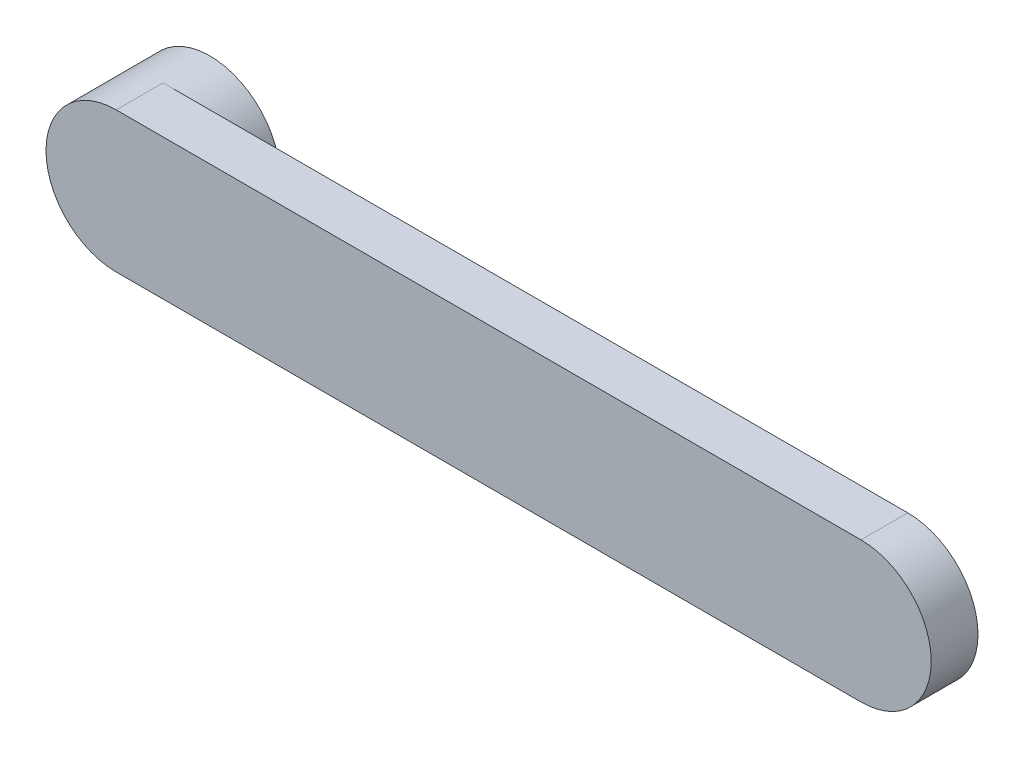
SolidWorks part; units mm, degrees
ref_plane "前视基准面" through (0, 0, 0) normal (0, 0, 1) x (1, 0, 0)
ref_plane "上视基准面" through (0, 0, 0) normal (0, 1, 0) x (1, 0, 0)
ref_plane "右视基准面" through (0, 0, 0) normal (1, 0, 0) x (0, 0, -1)
sketch "草图1" plane through (0, 0, 0) normal (0, 0, 1) x (1, 0, 0)
  line L3 (159.099, 30) -> (-159.099, 30)
  line L4 (-159.099, -30) -> (159.099, -30)
  arc A2 (-159.099, 30) -> (-159.099, -30) centre (-159.099, 0) ccw
  arc A3 (159.099, 30) -> (159.099, -30) centre (159.099, 0) cw
  point P6 (0, -30)
extrude "凸台-拉伸1" add sketch "草图1" along normal blind 10 and the other way blind 10
sketch "草图2" plane through (0, 0, 0) normal (0, 0, 1) x (1, 0, 0)
  circle A0 centre (-159.099, 0) radius 30
extrude "凸台-拉伸2" add sketch "草图2" against normal blind 30
